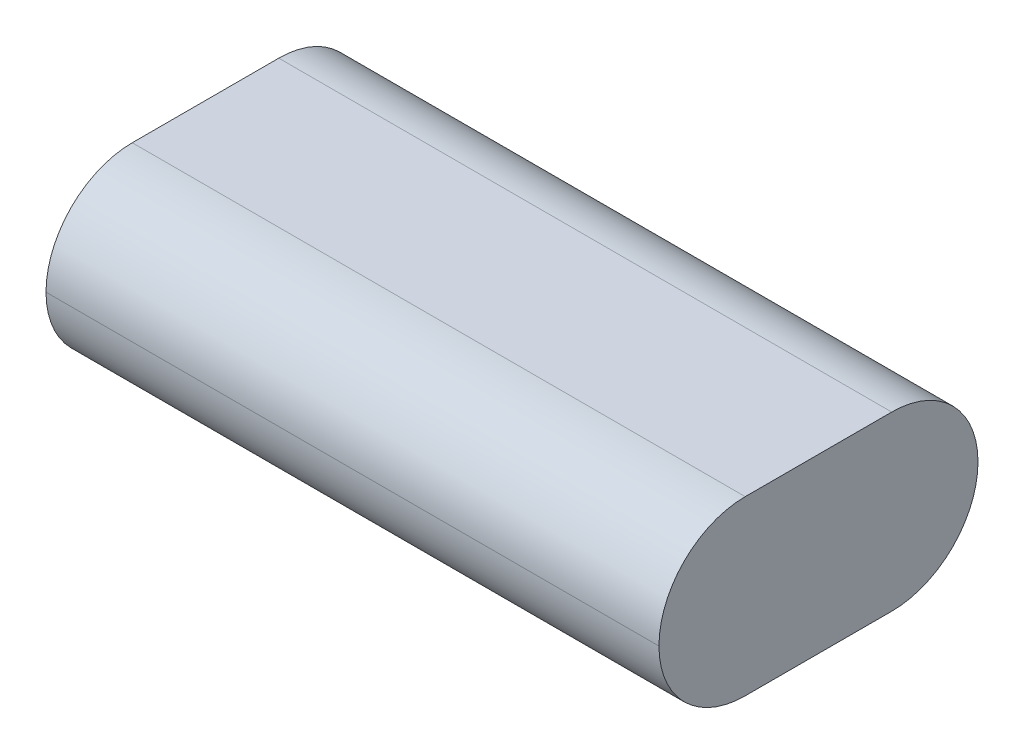
SolidWorks part; units mm, degrees
ref_plane "Front Plane" through (0, 0, 0) normal (0, 0, 1) x (1, 0, 0)
ref_plane "Top Plane" through (0, 0, 0) normal (0, 1, 0) x (1, 0, 0)
ref_plane "Right Plane" through (0, 0, 0) normal (1, 0, 0) x (0, 0, -1)
sketch "Sketch1" plane through (0, 0, 0) normal (0, 1, 0) x (1, 0, 0)
  line L1 (0, 0) -> (70.7, 0)
  line L2 (0, 0) -> (0, 36.8)
  line L3 (0, 36.8) -> (70.7, 36.8)
  line L4 (70.7, 0) -> (70.7, 36.8)
  dimension "D1" = 70.7
  dimension "D2" = 36.8
extrude "Boss-Extrude1" add sketch "Sketch1" along normal blind 19.9
fillet "Fillet1" radius 9.95 4 edges at (35.35, 19.9, -36.8) (35.35, 0, -36.8) (35.35, 0, 0) (35.35, 19.9, 0)
